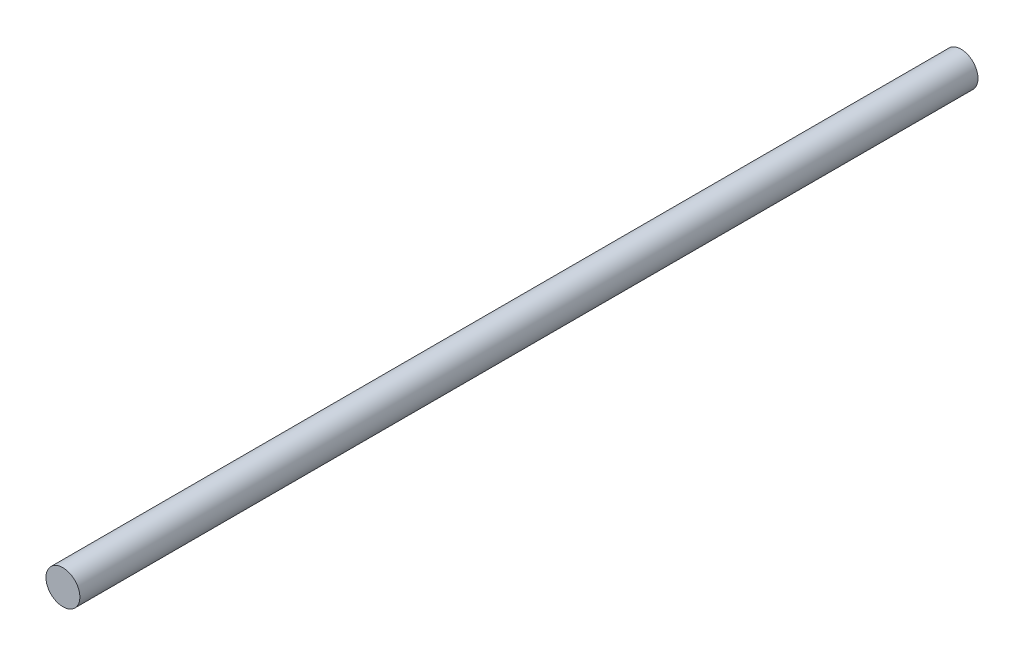
SolidWorks part; units mm, degrees
material "Pine"
ref_plane "Front Plane" through (0, 0, 0) normal (0, 0, 1) x (1, 0, 0)
ref_plane "Top Plane" through (0, 0, 0) normal (0, 1, 0) x (1, 0, 0)
ref_plane "Right Plane" through (0, 0, 0) normal (1, 0, 0) x (0, 0, -1)
ref_axis "X-Axis" through (-88.99, 0, 0) along (1, 0, 0)
ref_axis "Y-Axis" through (0, 55, 0) along (0, -1, 0)
ref_axis "Z-Axis" through (0, 0, -88.99) along (0, 0, 1)
sketch "Sketch1" plane through (0, 0, 0) normal (0, 0, 1) x (1, 0, 0)
  circle A0 centre (-142.875, 0) radius 3.175 construction
  circle A1 centre (-142.875, 0) radius 3.175
extrude "Boss-Extrude1" add sketch "Sketch1" along normal mid plane 168.275
